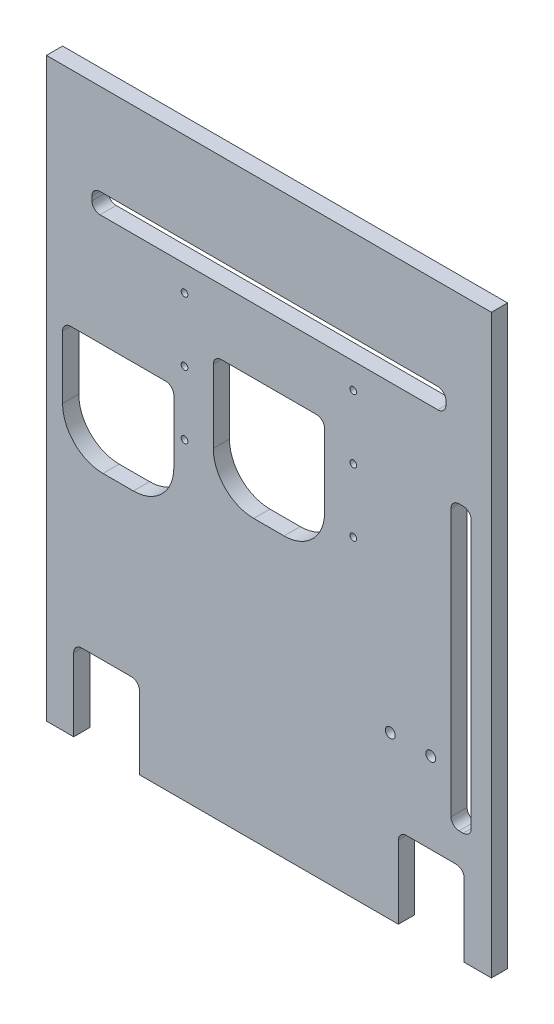
SolidWorks part; units mm, degrees
ref_plane "Front" through (0, 0, 0) normal (0, 0, 1) x (1, 0, 0)
ref_plane "Top" through (0, 0, 0) normal (0, 1, 0) x (1, 0, 0)
ref_plane "Right" through (0, 0, 0) normal (1, 0, 0) x (0, 0, -1)
sketch "Esquisse1" plane through (0, 0, 0) normal (0, 0, 1) x (1, 0, 0)
  line L1 (0, 0) -> (220, 0)
  line L2 (0, 0) -> (0, 285)
  line L3 (0, 285) -> (220, 285)
  line L4 (220, 0) -> (220, 285)
  dimension "D1" = 220
  dimension "D2" = 285
extrude "Boss.-Extru.1" add sketch "Esquisse1" along normal blind 8
sketch "Esquisse2" plane through (0, 0, 0) normal (0, -1, 0) x (1, 0, 0)
  line L0 (0, 4) -> (220, 4) construction
  line L1 (0, 8) -> (0, 0) construction
  line L2 (220, 8) -> (220, 0) construction
  line L3 (110, 4) -> (110, 28.0559) construction
  circle A0 centre (110, 4) radius 2
  circle A1 centre (213, 4) radius 2
  circle A2 centre (7, 4) radius 2
  dimension "D1" = 4
  dimension "D2" = 103
extrude "Enlèv. mat.-Extru.1" cut sketch "Esquisse2" against normal blind 10
sketch "Esquisse3" plane through (0, 0, 8) normal (0, 0, 1) x (1, 0, 0)
  line L0 (110, 0) -> (110, 285) construction
  line L1 (0, 0) -> (220, 0) construction
  line L2 (220, 285) -> (0, 285) construction
  line L3 (82.5, 198) -> (137.5, 198)
  line L4 (137.5, 198) -> (137.5, 138)
  line L5 (137.5, 138) -> (82.5, 138)
  line L6 (82.5, 198) -> (82.5, 138)
  line L8 (8, 175) -> (63, 175)
  line L9 (8, 175) -> (8, 120)
  line L10 (8, 120) -> (63, 120)
  line L11 (63, 175) -> (63, 120)
  line L12 (200, 55) -> (210, 55)
  line L13 (200, 55) -> (200, 195)
  line L14 (200, 195) -> (210, 195)
  line L15 (210, 55) -> (210, 195)
  point P11 (110, 138)
  point P12 (110, 198)
  dimension "D1" = 60
  dimension "D2" = 55
  dimension "D3" = 138
  dimension "D4" = 55
  dimension "D5" = 47
  dimension "D6" = 55
  dimension "D7" = 120
  dimension "D8" = 140
  dimension "D9" = 55
  dimension "D10" = 90
  dimension "D11" = 10
extrude "Enlèv. mat.-Extru.2" cut sketch "Esquisse3" against normal through all both and the other way through all
sketch "Esquisse5" plane through (0, 0, 8) normal (0, 0, 1) x (1, 0, 0)
  line L0 (110, 230) -> (110, 0) construction
  line L1 (22.5, 240) -> (197.5, 240)
  line L2 (22.5, 240) -> (22.5, 230)
  line L3 (22.5, 230) -> (197.5, 230)
  line L4 (197.5, 240) -> (197.5, 230)
  line L5 (0, 0) -> (220, 0) construction
  dimension "D1" = 175
  dimension "D2" = 10
  dimension "D3" = 230
extrude "Enlèv. mat.-Extru.3" cut sketch "Esquisse5" against normal through all both and the other way through all
sketch "Esquisse6" plane through (0, 0, 8) normal (0, 0, 1) x (1, 0, 0)
  line L0 (170, 80) -> (190, 80) construction
  line L1 (0, 0) -> (220, 0) construction
  line L2 (137.5, 138) -> (82.5, 138) construction
  circle A0 centre (190, 80) radius 2.45
  circle A1 centre (170, 80) radius 2.45
  point P8 (110, 138)
  dimension "D1" = 4.9
  dimension "D3" = 80
  dimension "D2" = 20
  dimension "D4" = 60
extrude "Enlèv. mat.-Extru.4" cut sketch "Esquisse6" against normal through all both and the other way through all
sketch "Esquisse7" plane through (0, 0, 8) normal (0, 0, 1) x (1, 0, 0)
  line L0 (110, 0) -> (110, 285) construction
  line L1 (0, 0) -> (220, 0) construction
  line L2 (220, 285) -> (0, 285) construction
  line L3 (68.285, 186) -> (68.285, 217.4) construction
  line L4 (68.285, 186) -> (110, 186) construction
  line L5 (151.715, 186) -> (151.715, 217.4) construction
  circle A0 centre (68.285, 217.4) radius 1.65
  circle A1 centre (68.285, 186) radius 1.65
  circle A2 centre (68.285, 154.6) radius 1.65
  circle A3 centre (151.715, 154.6) radius 1.65
  circle A4 centre (151.715, 186) radius 1.65
  circle A5 centre (151.715, 217.4) radius 1.65
  dimension "D1" = 31.4
  dimension "D2" = 3.3
  dimension "D3" = 83.43
  dimension "D4" = 186
extrude "Enlèv. mat.-Extru.5" cut sketch "Esquisse7" against normal through all both and the other way through all
sketch "Esquisse8" plane through (0, 0, 8) normal (0, 0, 1) x (1, 0, 0)
  line L0 (110, 0) -> (110, 285) construction
  line L1 (0, 0) -> (220, 0) construction
  line L2 (220, 285) -> (0, 285) construction
  line L3 (174, 0) -> (174, 40)
  line L4 (13.5, 0) -> (46, 0)
  line L5 (13.5, 0) -> (13.5, 40)
  line L6 (13.5, 40) -> (46, 40)
  line L7 (46, 0) -> (46, 40)
  line L8 (206.5, 40) -> (174, 40)
  line L9 (206.5, 0) -> (206.5, 40)
  line L10 (206.5, 0) -> (174, 0)
  dimension "D1" = 128
  dimension "D2" = 32.5
  dimension "D3" = 40
extrude "Enlèv. mat.-Extru.6" cut sketch "Esquisse8" against normal through all both and the other way through all
fillet "Congé1" radius 20 4 edges at (137.5, 138, 4) (82.5, 138, 4) (63, 120, 4) (8, 120, 4)
fillet "Congé2" radius 4 16 edges at (137.5, 198, 4) (82.5, 198, 4) (197.5, 230, 4) (197.5, 240, 4) (22.5, 240, 4) (22.5, 230, 4) (63, 175, 4) (8, 175, 4) (200, 195, 4) (210, 195, 4) (210, 55, 4) (200, 55, 4) (206.5, 40, 4) (174, 40, 4) (46, 40, 4) (13.5, 40, 4)
